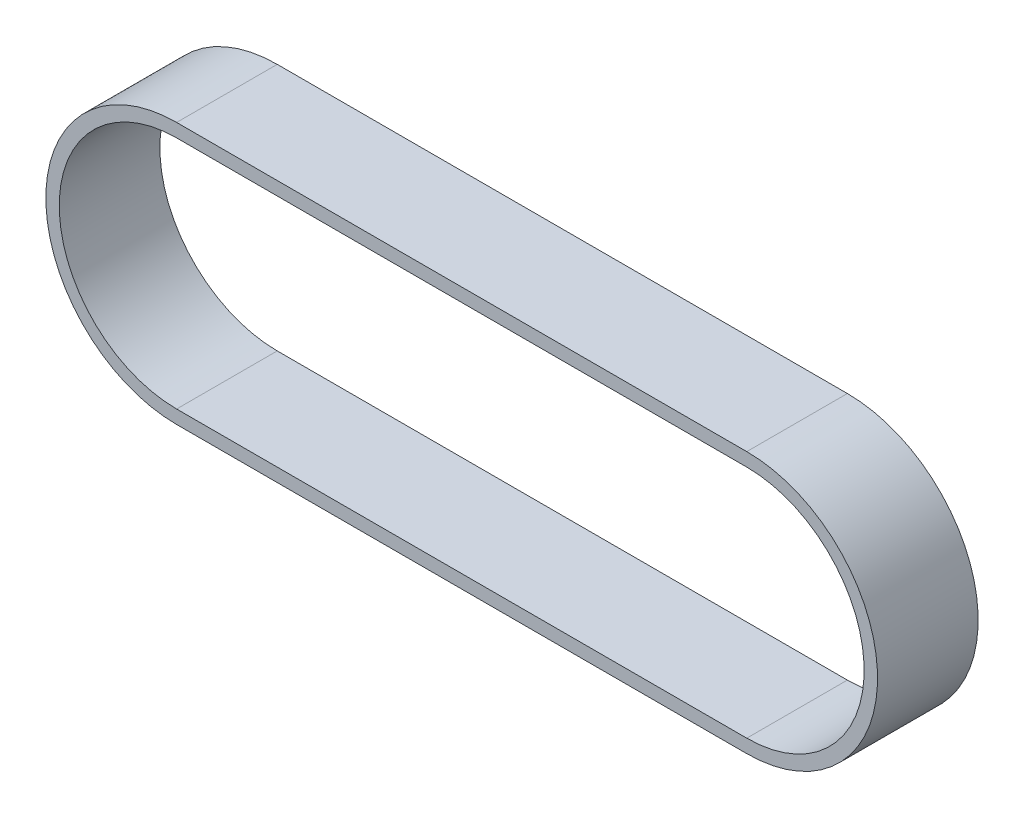
SolidWorks part; units mm, degrees
material "Silicon Rubber"
ref_plane "Front Plane" through (0, 0, 0) normal (0, 0, 1) x (1, 0, 0)
ref_plane "Top Plane" through (0, 0, 0) normal (0, 1, 0) x (1, 0, 0)
ref_plane "Right Plane" through (0, 0, 0) normal (1, 0, 0) x (0, 0, -1)
sketch "Sketch1" plane through (0, 0, 0) normal (0, 0, 1) x (1, 0, 0)
  line L0 (-20.3819, 0) -> (25.0953, 0) construction
  line L1 (-42.5, 17.5) -> (42.5, 17.5)
  line L2 (0, 23.3367) -> (0, -30.4014) construction
  line L3 (-42.5, -17.5) -> (42.5, -17.5)
  line L4 (-42.5, 19.5) -> (42.5, 19.5)
  line L5 (-42.5, -19.5) -> (42.5, -19.5)
  arc A0 (-42.5, -17.5) -> (-42.5, 17.5) centre (-42.5, 0) cw
  arc A1 (42.5, 17.5) -> (42.5, -17.5) centre (42.5, 0) cw
  arc A2 (42.5, 19.5) -> (42.5, -19.5) centre (42.5, 0) cw
  arc A3 (-42.5, -19.5) -> (-42.5, 19.5) centre (-42.5, 0) cw
  dimension "D2" = 17.5
  dimension "D1" = 85
  dimension "D3" = 2
extrude "Boss-Extrude1" add sketch "Sketch1" along normal blind 7.5 and the other way blind 7.5
